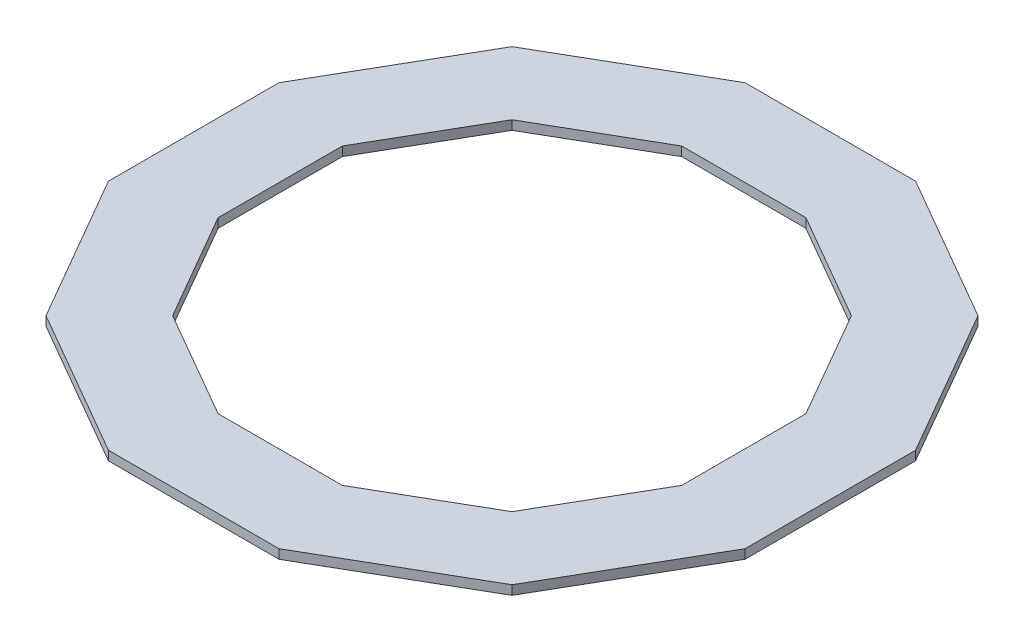
SolidWorks part; units mm, degrees
material "ABS PC"
ref_plane "Front Plane" through (0, 0, 0) normal (0, 0, 1) x (1, 0, 0)
ref_plane "Top Plane" through (0, 0, 0) normal (0, 1, 0) x (1, 0, 0)
ref_plane "Right Plane" through (0, 0, 0) normal (1, 0, 0) x (0, 0, -1)
sketch "Sketch1" plane through (0, 0, 0) normal (0, 1, 0) x (1, 0, 0)
  line L0 (26.296, 98.1381) -> (-26.296, 98.1381)
  line L1 (-26.296, 98.1381) -> (-71.842, 71.842)
  line L2 (-71.842, 71.842) -> (-98.1381, 26.296)
  line L3 (-98.1381, 26.296) -> (-98.1381, -26.296)
  line L4 (-98.1381, -26.296) -> (-71.842, -71.842)
  line L5 (-71.842, -71.842) -> (-26.296, -98.1381)
  line L6 (-26.296, -98.1381) -> (26.296, -98.1381)
  line L7 (26.296, -98.1381) -> (71.842, -71.842)
  line L8 (71.842, -71.842) -> (98.1381, -26.296)
  line L9 (98.1381, -26.296) -> (98.1381, 26.296)
  line L10 (98.1381, 26.296) -> (71.842, 71.842)
  line L11 (71.842, 71.842) -> (26.296, 98.1381)
  circle A0 centre (0, 0) radius 101.6
  dimension "D1" = 203.2
extrude "Boss-Extrude1" add sketch "Sketch1" against normal blind 2.921 contours L10 L11 L0 L1 L2 L3 L4 L5 L6 L7 L8 L9 region at (0, 0, 0)
sketch "Sketch3" plane through (0, 0, 0) normal (0, 1, 0) x (1, 0, 0)
  line L12 (-53.8815, 53.8815) -> (-19.722, 73.6035)
  line L13 (-19.722, 73.6035) -> (19.722, 73.6035)
  line L14 (19.722, 73.6035) -> (53.8815, 53.8815)
  line L15 (53.8815, 53.8815) -> (73.6035, 19.722)
  line L16 (73.6035, 19.722) -> (73.6035, -19.722)
  line L17 (73.6035, -19.722) -> (53.8815, -53.8815)
  line L18 (53.8815, -53.8815) -> (19.722, -73.6035)
  line L19 (19.722, -73.6035) -> (-19.722, -73.6035)
  line L20 (-19.722, -73.6035) -> (-53.8815, -53.8815)
  line L21 (-53.8815, -53.8815) -> (-73.6035, -19.722)
  line L22 (-73.6035, -19.722) -> (-73.6035, 19.722)
  line L23 (-73.6035, 19.722) -> (-53.8815, 53.8815)
  line L24 (-71.842, 71.842) -> (-98.1381, 26.296) construction
  line L25 (-26.296, 98.1381) -> (-71.842, 71.842) construction
  line L26 (26.296, 98.1381) -> (-26.296, 98.1381) construction
  line L27 (71.842, 71.842) -> (26.296, 98.1381) construction
  line L28 (98.1381, 26.296) -> (71.842, 71.842) construction
  line L29 (98.1381, -26.296) -> (98.1381, 26.296) construction
  line L30 (71.842, -71.842) -> (98.1381, -26.296) construction
  line L31 (26.296, -98.1381) -> (71.842, -71.842) construction
  line L32 (-26.296, -98.1381) -> (26.296, -98.1381) construction
  line L33 (-71.842, -71.842) -> (-26.296, -98.1381) construction
  line L34 (-98.1381, -26.296) -> (-71.842, -71.842) construction
  line L35 (-98.1381, 26.296) -> (-98.1381, -26.296) construction
  line L36 (-26.296, 98.1381) -> (26.296, -98.1381) construction
  line L37 (26.296, 98.1381) -> (-26.296, -98.1381) construction
  circle A0 centre (0, 0) radius 76.2
  dimension "D1" = 152.4
extrude "Cut-Extrude1" cut sketch "Sketch3" against normal through all contours L23 L22 L21 L20 L19 L18 L17 L16 L15 L14 L13 L12 region at (0, 0, 0)
sketch "Sketch4" plane through (0, 0, 0) normal (0, 1, 0) x (1, 0, 0)
  line L24 (101.0591, 27.0787) -> (73.9804, 73.9804)
  line L25 (73.9804, 73.9804) -> (27.0787, 101.0591)
  line L26 (27.0787, 101.0591) -> (-27.0787, 101.0591)
  line L27 (-27.0787, 101.0591) -> (-73.9804, 73.9804)
  line L28 (-73.9804, 73.9804) -> (-101.0591, 27.0787)
  line L29 (-101.0591, 27.0787) -> (-101.0591, -27.0787)
  line L30 (-101.0591, -27.0787) -> (-73.9804, -73.9804)
  line L31 (-73.9804, -73.9804) -> (-27.0787, -101.0591)
  line L32 (-27.0787, -101.0591) -> (27.0787, -101.0591)
  line L33 (27.0787, -101.0591) -> (73.9804, -73.9804)
  line L34 (73.9804, -73.9804) -> (101.0591, -27.0787)
  line L35 (101.0591, -27.0787) -> (101.0591, 27.0787)
  line L36 (101.0591, 27.0787) -> (73.9804, 73.9804)
  line L37 (73.9804, 73.9804) -> (27.0787, 101.0591)
  line L38 (27.0787, 101.0591) -> (-27.0787, 101.0591)
  line L39 (-27.0787, 101.0591) -> (-73.9804, 73.9804)
  line L40 (-73.9804, 73.9804) -> (-101.0591, 27.0787)
  line L41 (-101.0591, 27.0787) -> (-101.0591, -27.0787)
  line L42 (-101.0591, -27.0787) -> (-73.9804, -73.9804)
  line L43 (-73.9804, -73.9804) -> (-27.0787, -101.0591)
  line L44 (-27.0787, -101.0591) -> (27.0787, -101.0591)
  line L45 (27.0787, -101.0591) -> (73.9804, -73.9804)
  line L46 (73.9804, -73.9804) -> (101.0591, -27.0787)
  line L47 (101.0591, -27.0787) -> (101.0591, 27.0787)
  line L60 (98.1381, 26.296) -> (71.842, 71.842)
  line L61 (71.842, 71.842) -> (26.296, 98.1381)
  line L62 (26.296, 98.1381) -> (-26.296, 98.1381)
  line L63 (-26.296, 98.1381) -> (-71.842, 71.842)
  line L64 (-71.842, 71.842) -> (-98.1381, 26.296)
  line L65 (-98.1381, 26.296) -> (-98.1381, -26.296)
  line L66 (-98.1381, -26.296) -> (-71.842, -71.842)
  line L67 (-71.842, -71.842) -> (-26.296, -98.1381)
  line L68 (-26.296, -98.1381) -> (26.296, -98.1381)
  line L69 (26.296, -98.1381) -> (71.842, -71.842)
  line L70 (71.842, -71.842) -> (98.1381, -26.296)
  line L71 (98.1381, -26.296) -> (98.1381, 26.296)
  line L72 (98.1381, 26.296) -> (71.842, 71.842)
  line L73 (71.842, 71.842) -> (26.296, 98.1381)
  line L74 (26.296, 98.1381) -> (-26.296, 98.1381)
  line L75 (-26.296, 98.1381) -> (-71.842, 71.842)
  line L76 (-71.842, 71.842) -> (-98.1381, 26.296)
  line L77 (-98.1381, 26.296) -> (-98.1381, -26.296)
  line L78 (-98.1381, -26.296) -> (-71.842, -71.842)
  line L79 (-71.842, -71.842) -> (-26.296, -98.1381)
  line L80 (-26.296, -98.1381) -> (26.296, -98.1381)
  line L81 (26.296, -98.1381) -> (71.842, -71.842)
  line L82 (71.842, -71.842) -> (98.1381, -26.296)
  line L83 (98.1381, -26.296) -> (98.1381, 26.296)
  circle A0 centre (0, 0) radius 104.624
  line M25 (98.1381, 26.296) -> (71.842, 71.842)
  line M26 (71.842, 71.842) -> (26.296, 98.1381)
  line M27 (26.296, 98.1381) -> (-26.296, 98.1381)
  line M28 (-26.296, 98.1381) -> (-71.842, 71.842)
  line M29 (-71.842, 71.842) -> (-98.1381, 26.296)
  line M30 (-98.1381, 26.296) -> (-98.1381, -26.296)
  line M31 (-98.1381, -26.296) -> (-71.842, -71.842)
  line M32 (-71.842, -71.842) -> (-26.296, -98.1381)
  line M33 (-26.296, -98.1381) -> (26.296, -98.1381)
  line M34 (26.296, -98.1381) -> (71.842, -71.842)
  line M35 (71.842, -71.842) -> (98.1381, -26.296)
  line M36 (98.1381, -26.296) -> (98.1381, 26.296)
  dimension "D1" = 2.921
  dimension "D2" = 0
extrude "Boss-Extrude2" add sketch "Sketch4" against normal up to surface (2.921 mm away) contours L46 L47 L36 L37 L38 L39 L40 L41 L42 L43 L44 L45 M25 M36 M35 M34 M33 M32 M31 M30 M29 M28 M27 M26 region at (98.2007, 0, 0) up to face at (0, -2.921, 0)
